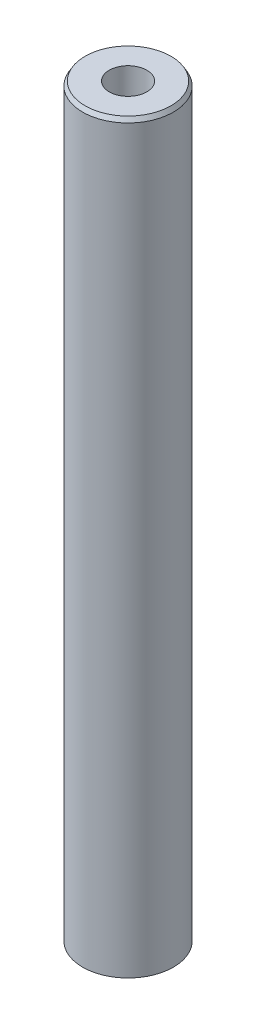
SolidWorks part; units mm, degrees
ref_plane "Front Plane" through (0, 0, 0) normal (0, 0, 1) x (1, 0, 0)
ref_plane "Top Plane" through (0, 0, 0) normal (0, 1, 0) x (1, 0, 0)
ref_plane "Right Plane" through (0, 0, 0) normal (1, 0, 0) x (0, 0, -1)
sketch "Sketch1" plane through (0, 0, 0) normal (0, 1, 0) x (1, 0, 0)
  circle A0 centre (0, 0) radius 10
  dimension "SHAFT_OD" = 20
extrude "Boss-Extrude1" add sketch "Sketch1" along normal blind 164.6076
sketch "Sketch2" plane through (0, 0, 0) normal (0, 1, 0) x (1, 0, 0)
  circle A0 centre (0, 0) radius 4.141
  dimension "BORE_D" = 8.2819
extrude "Cut-Extrude1" cut sketch "Sketch2" along normal through all
chamfer "Chamfer1" distance 0.938 angle 30 2 edges at (0, 164.6076, 10) (0, 0, 10) first distance on face at (0, 164.6076, 10) first distance on face at (0, 0, 4.141)
